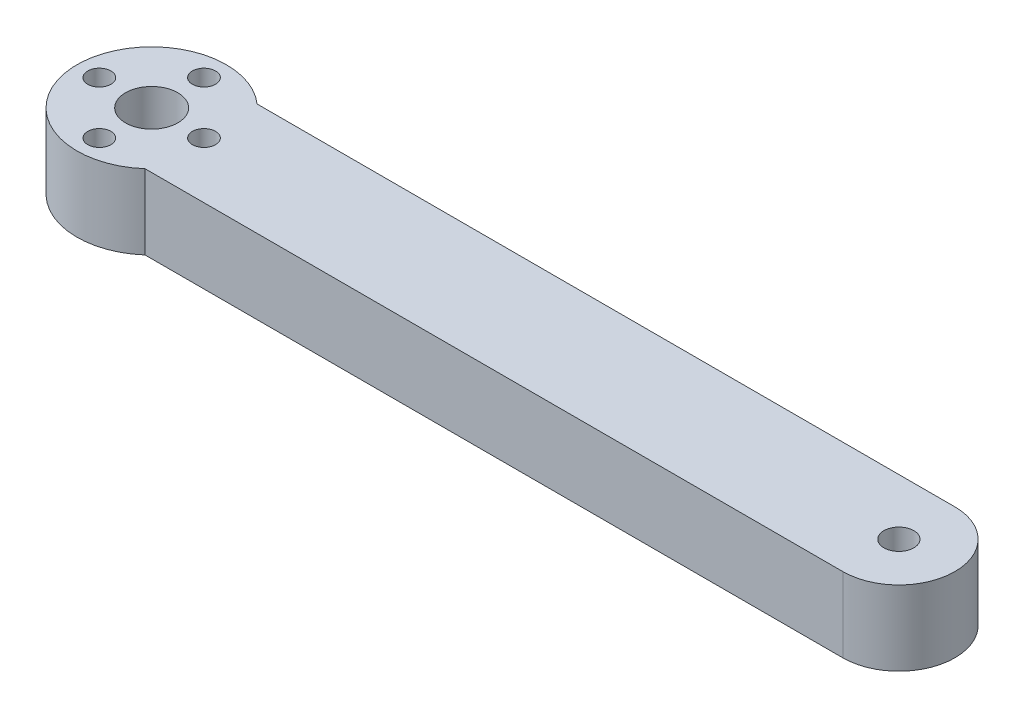
SolidWorks part; units mm, degrees
ref_plane "Front Plane" through (0, 0, 0) normal (0, 0, 1) x (1, 0, 0)
ref_plane "Top Plane" through (0, 0, 0) normal (0, 1, 0) x (1, 0, 0)
ref_plane "Right Plane" through (0, 0, 0) normal (1, 0, 0) x (0, 0, -1)
sketch "Sketch2" plane through (0, 0, 0) normal (0, 1, 0) x (1, 0, 0)
  line L0 (0, 0) -> (100, 0) construction
  line L1 (0, 7.5) -> (100, 7.5)
  line L2 (0, -7.5) -> (100, -7.5)
  arc A0 (0, 7.5) -> (0, -7.5) centre (0, 0) ccw
  arc A1 (100, -7.5) -> (100, 7.5) centre (100, 0) ccw
  circle A2 centre (0, 0) radius 2.5
  circle A3 centre (100, 0) radius 2
  point P3 (50, 0)
  dimension "D2" = 5
  dimension "D4" = 4
  dimension "D1" = 100
  dimension "D3" = 15
extrude "Boss-Extrude1" add sketch "Sketch2" along normal blind 10
sketch "Sketch4" plane through (0, 0, -7.5) normal (0, 0, -1) x (-1, 0, 0)
  line L0 (0, 10) -> (0, 0) construction
  circle A0 centre (0, 5) radius 1.5
extrude "Cut-Extrude3" cut sketch "Sketch4" against normal through all
sketch "Sketch5" plane through (0, 10, 0) normal (0, 1, 0) x (1, 0, 0)
  line L1 (100, 7.5) -> (0, 7.5) construction
  line L2 (114.9191, 7.5) -> (100, 7.5)
  line L4 (0, -7.5) -> (100, -7.5) construction
  line L5 (115.1207, -7.5) -> (100, -7.5)
  line L6 (112.5, -7.5) -> (112.5, 7.5)
  line L7 (112.5, 7.5) -> (114.9191, 7.5)
  line L9 (112.5, -7.5) -> (115.1207, -7.5)
  arc A0 (100, -7.5) -> (100, 7.5) centre (100, 0) ccw
extrude "Cut-Extrude5" [suppressed] cut sketch "Sketch5" against normal blind 3
sketch "Sketch6" [suppressed] plane through (0, 10, 0) normal (0, 1, 0) x (1, 0, 0)
  line L1 (112.5, 7.5) -> (120, 7.5)
  line L2 (120, -7.5) -> (112.5, -7.5)
  line L5 (112.5, 7.5) -> (112.5, -7.5) construction
  line L6 (112.5, 7.5) -> (112.5, -7.5)
  arc A1 (120, 7.5) -> (127.5, 0) centre (120, 0) cw
  arc A2 (120, -7.5) -> (120, 7.5) centre (120, 0) ccw construction
  arc A3 (127.5, 0) -> (120, -7.5) centre (120, 0) cw
extrude "Cut-Extrude6" [suppressed] cut sketch "Sketch6" against normal up to next from offset 7 offset against normal yes
sketch "Sketch7" plane through (0, 10, 0) normal (0, 1, 0) x (1, 0, 0)
  circle A0 centre (0, 0) radius 10
  dimension "D1" = 20
extrude "Boss-Extrude4" add sketch "Sketch7" against normal blind 10
sketch "Sketch8" plane through (0, 10, 0) normal (0, 1, 0) x (1, 0, 0)
  line L0 (0, -7) -> (0, 7) construction
  line L1 (-7, 0) -> (7, 0) construction
  circle A0 centre (0, 7) radius 1.55
  circle A1 centre (7, 0) radius 1.55
  circle A2 centre (0, -7) radius 1.55
  circle A3 centre (-7, 0) radius 1.55
  circle A4 centre (0, 0) radius 3.5
  point P4 (0, 0)
  point P8 (0, 0)
extrude "Cut-Extrude7" cut sketch "Sketch8" against normal blind 10
